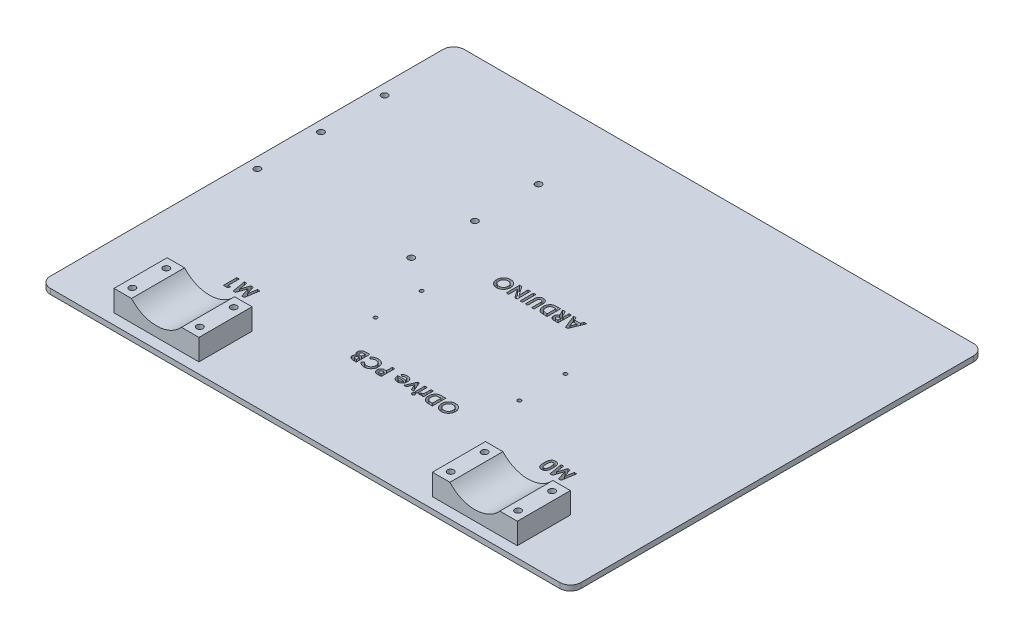
SolidWorks part; units mm, degrees
ref_plane "Plan de face" through (0, 0, 0) normal (0, 0, 1) x (1, 0, 0)
ref_plane "Plan de dessus" through (0, 0, 0) normal (0, 1, 0) x (1, 0, 0)
ref_plane "Plan de droite" through (0, 0, 0) normal (1, 0, 0) x (0, 0, -1)
sketch "Esquisse1" plane through (0, 0, 0) normal (0, 1, 0) x (1, 0, 0)
  line L1 (240, -150) -> (-240, -150)
  line L2 (250, -140) -> (250, 140)
  line L3 (240, 150) -> (-240, 150)
  line L4 (-250, -140) -> (-250, 140)
  line L5 (250, -150) -> (-250, 150) construction
  line L6 (250, 150) -> (-250, -150) construction
  arc A0 (-240, -150) -> (-250, -140) centre (-240, -140) cw
  arc A1 (240, -150) -> (250, -140) centre (240, -140) ccw
  arc A2 (250, 140) -> (240, 150) centre (240, 140) ccw
  arc A3 (-240, 150) -> (-250, 140) centre (-240, 140) ccw
  point P0 (0, 0)
  dimension "D3" = 10
  dimension "D1" = 300
  dimension "D2" = 500
extrude "Boss.-Extru.1" add sketch "Esquisse1" along normal blind 5
sketch "Esquisse2" plane through (0, 5, 0) normal (0, 1, 0) x (1, 0, 0)
  line L0 (240, 150) -> (-240, 150) construction
  line L1 (-240, -150) -> (240, -150) construction
  line L2 (250, -140) -> (250, 140) construction
  line L3 (-250, 140) -> (-250, -140) construction
  spline S4 degree 3 poles (74.2, -20.6163) (74.2, -17.2163) (70.8, -17.2163) (70.8, -20.6163) (70.8, -24.0163) (74.2, -24.0163) (74.2, -20.6163) (74.2, -17.2163) (70.8, -17.2163) knots -0.5 0 0 0 0.5 0.5 0.5 1 1 1 1.5 1.5 1.5 weights 1 0.333333 0.333333 1 0.333333 0.333333 1 0.333333 0.333333 only from (74.2, -20.6163) to (74.2, -20.6163)
  spline S5 degree 3 poles (74.2, 22.8837) (74.2, 26.2837) (70.8, 26.2837) (70.8, 22.8837) (70.8, 19.4837) (74.2, 19.4837) (74.2, 22.8837) (74.2, 26.2837) (70.8, 26.2837) knots -0.5 0 0 0 0.5 0.5 0.5 1 1 1 1.5 1.5 1.5 weights 1 0.333333 0.333333 1 0.333333 0.333333 1 0.333333 0.333333 only from (74.2, 22.8837) to (74.2, 22.8837)
  spline S6 degree 3 poles (-61.3, -20.6162) (-61.3, -17.2162) (-64.7, -17.2162) (-64.7, -20.6162) (-64.7, -24.0162) (-61.3, -24.0162) (-61.3, -20.6162) (-61.3, -17.2162) (-64.7, -17.2162) knots -0.5 0 0 0 0.5 0.5 0.5 1 1 1 1.5 1.5 1.5 weights 1 0.333333 0.333333 1 0.333333 0.333333 1 0.333333 0.333333 only from (-61.3, -20.6162) to (-61.3, -20.6162)
  spline S7 degree 3 poles (-61.3, 22.8838) (-61.3, 26.2837) (-64.7, 26.2838) (-64.7, 22.8838) (-64.7, 19.4838) (-61.3, 19.4838) (-61.3, 22.8838) (-61.3, 26.2837) (-64.7, 26.2838) knots -0.5 0 0 0 0.5 0.5 0.5 1 1 1 1.5 1.5 1.5 weights 1 0.333333 0.333333 1 0.333333 0.333333 1 0.333333 0.333333 only from (-61.3, 22.8838) to (-61.3, 22.8838)
  point P4 (0, 0)
  point P13 (-61.3, 22.8837)
  point P14 (-61.3, 22.8837)
  point P15 (-61.3, 22.8837)
  point P16 (-61.3, 22.8837)
  point P17 (0, 0)
  dimension "D1" = 127.1162
  dimension "D2" = 127.1163
  dimension "D3" = 129.3837
  dimension "D4" = 129.3838
  dimension "D5" = 135.5
  dimension "D6" = 175.8
  dimension "D7" = 175.8
  dimension "D8" = 188.7
extrude "Enlèv. mat.-Extru.1" cut sketch "Esquisse2" against normal through all contours S7 | S6 | S5 | S4
sketch "Esquisse3" plane through (0, 0, 150) normal (0, 0, 1) x (1, 0, 0)
  line L0 (-240, 5) -> (240, 5) construction
  line L1 (-190, 5) -> (-110, 5)
  line L2 (-190, 5) -> (-190, 25)
  line L3 (-190, 25) -> (-173.5557, 25)
  line L4 (-110, 5) -> (-110, 25)
  line L5 (-240, 5) -> (-240, 0) construction
  line L6 (-150, -5.8486) -> (-150, 68.1347) construction
  line L7 (-126.4443, 25) -> (-110, 25)
  arc A0 (-173.5557, 25) -> (-126.4443, 25) centre (-150, 45.9136) ccw
  point P12 (-155.3501, 45.9136)
  dimension "D4" = 63
  dimension "D1" = 80
  dimension "D2" = 20
  dimension "D3" = 50
  dimension "D5" = 20.9136
  dimension "D6" = 16.4443
extrude "Boss.-Extru.2" add sketch "Esquisse3" along normal blind 50 from offset 60 offset against normal yes
sketch "Esquisse4" plane through (0, 25, 0) normal (0, 1, 0) x (1, 0, 0)
  line L0 (-181.7778, -90) -> (-181.7778, -143.1865) construction
  line L1 (-173.5557, -90) -> (-190, -90) construction
  line L2 (-150, -90) -> (-150, -156.1953) construction
  line L3 (-190, -90) -> (-110, -90) construction
  line L4 (-173.5557, -140) -> (-190, -140) construction
  circle A0 centre (-181.7778, -99) radius 3
  circle A1 centre (-181.7778, -131) radius 3
  circle A2 centre (-118.2222, -131) radius 3
  circle A3 centre (-118.2222, -99) radius 3
  dimension "D1" = 6
  dimension "D2" = 6
  dimension "D4" = 9
  dimension "D3" = 9
extrude "Enlèv. mat.-Extru.2" cut sketch "Esquisse4" against normal through all
mirror "Symétrie1" about plane through (0, 0, 0) normal (1, 0, 0) of "Enlèv. mat.-Extru.2", "Boss.-Extru.2"
sketch "Esquisse5" plane through (0, 5, 0) normal (0, 1, 0) x (1, 0, 0)
  line L0 (250, -140) -> (250, 140) construction
  line L1 (-250, 140) -> (250, 140)
  line L2 (-250, 140) -> (-250, 240)
  line L3 (-250, 240) -> (250, 240)
  line L4 (250, 140) -> (250, 240)
  dimension "D1" = 100
extrude "Boss.-Extru.3" add sketch "Esquisse5" against normal up to surface (5 mm away) up to face at (118.2222, 0, 96)
fillet "Congé1" radius 10 2 edges at (-250, 2.5, -240) (250, 2.5, -240)
sketch "Esquisse6" plane through (0, 5, 0) normal (0, 1, 0) x (1, 0, 0)
  line L0 (-240, 256.0019) -> (-240, 35.9163) construction
  line L1 (-250, 230) -> (-250, -140) construction
  line L2 (240, 240) -> (-240, 240) construction
  circle A0 centre (-240, 165) radius 3
  circle A1 centre (-240, 105) radius 3
  circle A2 centre (-240, 45) radius 3
  circle A6 centre (-95, 165) radius 3
  circle A7 centre (-95, 105) radius 3
  circle A8 centre (-95, 45) radius 3
  dimension "D2" = 6
  dimension "D1" = 10
  dimension "D4" = 75
  dimension "D3" = 3
  dimension "D5" = 2
extrude "Enlèv. mat.-Extru.3" cut sketch "Esquisse6" against normal through all contours A2 | A1 | A0 | A6 | A7 | A8
sketch "Esquisse7" plane through (0, 0, 0) normal (0, -1, 0) x (1, 0, 0)
  line L0 (-250, -230) -> (-250, 140) construction
  line L1 (-237.5, 130) -> (-222.5, 130)
  line L2 (-237.5, 130) -> (-237.5, 115)
  line L3 (-237.5, 115) -> (-222.5, 115)
  line L4 (-222.5, 130) -> (-222.5, 115)
  line L5 (-237.5, 130) -> (-222.5, 115) construction
  line L6 (-237.5, 115) -> (-222.5, 130) construction
  line L7 (-240, 150) -> (240, 150) construction
  line L8 (0, 249.5345) -> (0, -298.3398) construction
  line L10 (-237.5, -212.5) -> (-222.5, -212.5)
  line L11 (-237.5, -212.5) -> (-237.5, -227.5)
  line L12 (-237.5, -227.5) -> (-222.5, -227.5)
  line L13 (-222.5, -212.5) -> (-222.5, -227.5)
  line L14 (-237.5, -212.5) -> (-222.5, -227.5) construction
  line L15 (-237.5, -227.5) -> (-222.5, -212.5) construction
  line L16 (240, -240) -> (-240, -240) construction
  line L17 (237.5, -227.5) -> (222.5, -212.5) construction
  line L18 (237.5, -212.5) -> (222.5, -227.5) construction
  line L19 (237.5, 115) -> (222.5, 130) construction
  line L20 (237.5, 130) -> (222.5, 115) construction
  line L21 (222.5, -212.5) -> (222.5, -227.5)
  line L22 (237.5, -227.5) -> (222.5, -227.5)
  line L23 (237.5, -212.5) -> (237.5, -227.5)
  line L24 (237.5, -212.5) -> (222.5, -212.5)
  line L25 (222.5, 130) -> (222.5, 115)
  line L26 (237.5, 115) -> (222.5, 115)
  line L27 (237.5, 130) -> (237.5, 115)
  line L28 (237.5, 130) -> (222.5, 130)
  point P0 (-230, 122.5)
  point P12 (-230, -220)
  point P19 (-226.0695, -240)
  point P28 (230, -220)
  point P29 (230, 122.5)
  dimension "D1" = 15
  dimension "D2" = 20
  dimension "D3" = 20
  dimension "D4" = 15
  dimension "D5" = 15
  dimension "D6" = 20
  dimension "D7" = 20
extrude "Boss.-Extru.4" add sketch "Esquisse7" along normal blind 10
fillet "Congé2" radius 5 32 edges at (222.5, 0, -220) (-230, 0, -212.5) (-230, 0, -227.5) (230, 0, -212.5) (230, 0, -227.5) (230, 0, 115) (-237.5, -5, -227.5) (-237.5, 0, -220) (-237.5, -5, -212.5) (-222.5, -5, -212.5) (-222.5, -5, -227.5) (-222.5, 0, -220) (237.5, -5, -212.5) (222.5, -5, -212.5) (222.5, -5, -227.5) (237.5, -5, -227.5) (237.5, 0, -220) (237.5, -5, 130) (237.5, -5, 115) (237.5, 0, 122.5) (230, 0, 130) (222.5, 0, 122.5) (222.5, -5, 115) (222.5, -5, 130) (-222.5, -5, 130) (-237.5, -5, 130) (-237.5, -5, 115) (-222.5, -5, 115) (-222.5, 0, 122.5) (-230, 0, 115) (-230, 0, 130) (-237.5, 0, 122.5)
sketch "Esquisse8" plane through (0, 5, 0) normal (0, 1, 0) x (1, 0, 0)
  line L0 (184.1896, -53.3453) -> (109.3581, -53.3453) construction
  line L1 (-112.9445, -53.3453) -> (-190.483, -53.3453) construction
  line L2 (73.0317, -53.3453) -> (-66.49, -53.3453) construction
  line L3 (68.9359, 73.7462) -> (-66.49, 73.7462) construction
  text T0 "<b>M0</b>" font "Century Gothic" height in points 48
  text T1 "<b>M1</b>" font "Century Gothic" height in points 48
  text T2 "<b>ODrive PCB</b>" font "Century Gothic" height in points 48
  text T3 "<b>ARDUINO</b>" font "Century Gothic" height in points 48
extrude "Enlèv. mat.-Extru.4" cut sketch "Esquisse8" against normal through all
